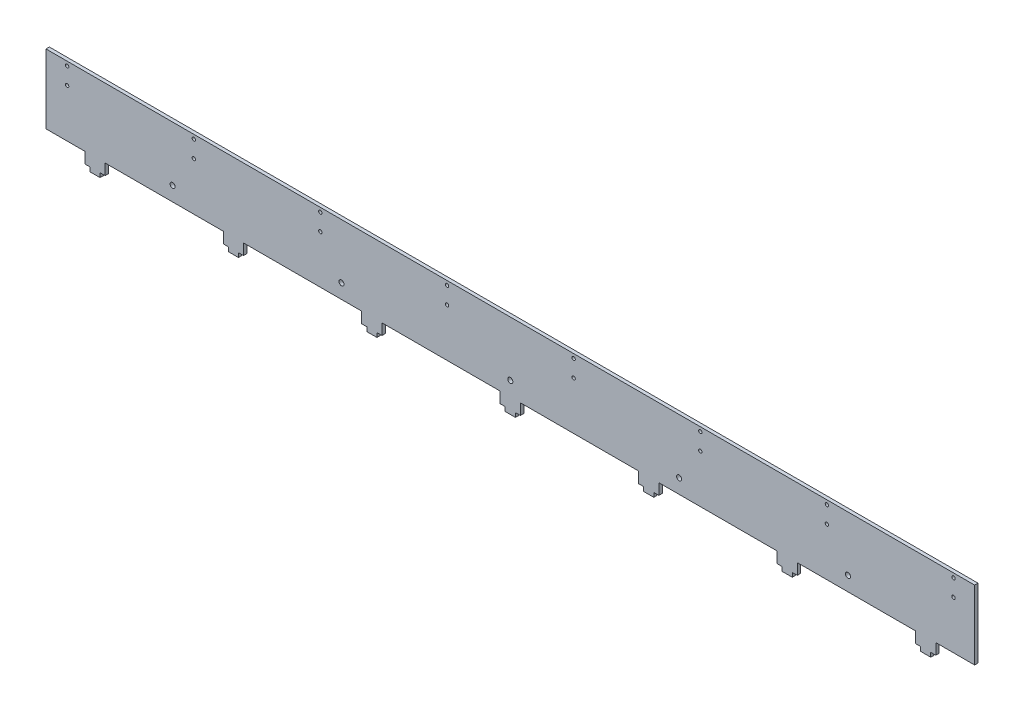
SolidWorks part; units mm, degrees
ref_plane "Спереди" through (0, 0, 0) normal (0, 0, 1) x (1, 0, 0)
ref_plane "Сверху" through (0, 0, 0) normal (0, 1, 0) x (1, 0, 0)
ref_plane "Справа" through (0, 0, 0) normal (1, 0, 0) x (0, 0, -1)
sketch "Эскиз1" plane through (0, 0, 0) normal (0, 0, 1) x (1, 0, 0)
  line L1 (-550, -47.5) -> (550, -47.5)
  line L2 (-550, -47.5) -> (-550, 47.5)
  line L3 (-550, 47.5) -> (550, 47.5)
  line L4 (550, -47.5) -> (550, 47.5)
  line L5 (0, 47.5) -> (0, -47.5) construction
  line L6 (-550, 0) -> (550, 0) construction
  point P0 (0, 0)
  dimension "D1" = 95
  dimension "D2" = 1100
extrude "Бобышка-Вытянуть1" add sketch "Эскиз1" along normal mid plane 4
sketch "Эскиз2" plane through (0, 0, 2) normal (0, 0, 1) x (1, 0, 0)
  line L0 (-550, -47.5) -> (550, -47.5) construction
  line L1 (-550, -47.5) -> (-504, -47.5)
  line L2 (-550, -47.5) -> (-550, -34.5)
  line L3 (-550, -34.5) -> (-504, -34.5)
  line L4 (-504, -47.5) -> (-504, -34.5)
  line L5 (550, -47.5) -> (504, -47.5)
  line L6 (550, -47.5) -> (550, -34.5)
  line L7 (550, -34.5) -> (504, -34.5)
  line L8 (504, -47.5) -> (504, -34.5)
  line L9 (-480, -34.5) -> (-340, -34.5)
  line L10 (-480, -34.5) -> (-480, -47.5)
  line L11 (-480, -47.5) -> (-340, -47.5)
  line L12 (-340, -34.5) -> (-340, -47.5)
  line L14 (-316, -34.5) -> (-176, -34.5)
  line L15 (-316, -34.5) -> (-316, -47.5)
  line L16 (-316, -47.5) -> (-176, -47.5)
  line L17 (-176, -34.5) -> (-176, -47.5)
  line L18 (-152, -34.5) -> (-12, -34.5)
  line L19 (-152, -34.5) -> (-152, -47.5)
  line L20 (-152, -47.5) -> (-12, -47.5)
  line L21 (-12, -34.5) -> (-12, -47.5)
  line L22 (12, -34.5) -> (152, -34.5)
  line L23 (12, -34.5) -> (12, -47.5)
  line L24 (12, -47.5) -> (152, -47.5)
  line L25 (152, -34.5) -> (152, -47.5)
  line L26 (176, -34.5) -> (316, -34.5)
  line L27 (176, -34.5) -> (176, -47.5)
  line L28 (176, -47.5) -> (316, -47.5)
  line L29 (316, -34.5) -> (316, -47.5)
  line L30 (340, -34.5) -> (480, -34.5)
  line L31 (340, -34.5) -> (340, -47.5)
  line L32 (340, -47.5) -> (480, -47.5)
  line L33 (480, -34.5) -> (480, -47.5)
  point P20 (-316, -41)
  point P25 (-152, -41)
  point P26 (152, -41)
  point P39 (340, -41)
  dimension "D1" = 13
  dimension "D5" = 24
  dimension "D6" = 140
  dimension "D7" = 24
  dimension "D2" = 24
  dimension "D3" = 140
  dimension "D4" = 140
  dimension "D8" = 24
  dimension "D9" = 140
  dimension "D10" = 24
  dimension "D11" = 140
  dimension "D12" = 24
  dimension "D13" = 140
  dimension "D14" = 24
extrude "Вырез-Вытянуть1" cut sketch "Эскиз2" against normal through all
sketch "Эскиз3" plane through (0, 0, 2) normal (0, 0, 1) x (1, 0, 0)
  line L0 (550, 47.5) -> (-550, 47.5) construction
  line L1 (-550, 47.5) -> (-550, -34.5) construction
  circle A0 centre (-525, 42.5) radius 2
  circle A1 centre (-525, 22.5) radius 2
  dimension "D1" = 4
  dimension "D2" = 5
  dimension "D3" = 20
  dimension "D4" = 25
extrude "Вырез-Вытянуть2" cut sketch "Эскиз3" against normal through all
pattern_linear "Линейный массив1" count 8 spacing 150 along (1, 0, 0) of "Вырез-Вытянуть2"
sketch "Эскиз4" plane through (0, 0, -2) normal (0, 0, -1) x (-1, 0, 0)
  circle A1 centre (-400, -17.5) radius 3
  circle A2 centre (-400, -17.5) radius 3
  dimension "D1" = 0
extrude "Вырез-Вытянуть3" cut sketch "Эскиз4" against normal through all
pattern_linear "Линейный массив2" count 5 spacing 200 along (-1, 0, 0) of "Вырез-Вытянуть3"
sketch "Эскиз5" plane through (0, -47.5, 0) normal (0, -1, 0) x (1, 0, 0)
  line L0 (492, -2) -> (492, 2) construction
  line L1 (480, 2) -> (504, 2) construction
  line L2 (328, -2) -> (328, 2) construction
  line L3 (316, -2) -> (340, -2) construction
  line L4 (504, 2) -> (480, 2)
  line L5 (480, 2) -> (480, -2)
  line L6 (480, -2) -> (504, -2)
  line L7 (504, -2) -> (504, 2)
  line L8 (498, 2) -> (486, 2)
  line L9 (486, 2) -> (486, -2)
  line L10 (486, -2) -> (498, -2)
  line L11 (498, -2) -> (498, 2)
  line L12 (316, 2) -> (340, 2) construction
  line L13 (164, -2) -> (164, 2) construction
  line L14 (316, -2) -> (340, -2)
  line L15 (340, -2) -> (340, 2)
  line L16 (340, 2) -> (316, 2)
  line L17 (316, 2) -> (316, -2)
  line L18 (322, -2) -> (334, -2)
  line L19 (334, -2) -> (334, 2)
  line L20 (334, 2) -> (322, 2)
  line L21 (322, 2) -> (322, -2)
  line L22 (152, -2) -> (176, -2) construction
  line L23 (152, 2) -> (176, 2) construction
  line L24 (0, -2) -> (0, 2) construction
  line L25 (176, 2) -> (152, 2)
  line L26 (152, 2) -> (152, -2)
  line L27 (152, -2) -> (176, -2)
  line L28 (176, -2) -> (176, 2)
  line L29 (170, 2) -> (158, 2)
  line L30 (158, 2) -> (158, -2)
  line L31 (158, -2) -> (170, -2)
  line L32 (170, -2) -> (170, 2)
  line L33 (-12, -2) -> (12, -2) construction
  line L34 (-12, 2) -> (12, 2) construction
  line L36 (-12, -2) -> (12, -2)
  line L37 (12, -2) -> (12, 2)
  line L38 (12, 2) -> (-12, 2)
  line L39 (-12, 2) -> (-12, -2)
  line L40 (-6, -2) -> (6, -2)
  line L41 (6, -2) -> (6, 2)
  line L42 (6, 2) -> (-6, 2)
  line L43 (-6, 2) -> (-6, -2)
  line L44 (-480, 2) -> (-504, 2) construction
  line L46 (-504, -2) -> (-480, -2) construction
  line L48 (-316, 2) -> (-340, 2) construction
  line L50 (-340, -2) -> (-316, -2) construction
  line L52 (-152, 2) -> (-176, 2) construction
  line L54 (-176, -2) -> (-152, -2) construction
  line L56 (-486, 2) -> (-498, 2)
  line L57 (-498, 2) -> (-498, -2)
  line L58 (-498, -2) -> (-486, -2)
  line L59 (-486, -2) -> (-486, 2)
  line L60 (-322, 2) -> (-334, 2)
  line L61 (-334, 2) -> (-334, -2)
  line L62 (-334, -2) -> (-322, -2)
  line L63 (-322, -2) -> (-322, 2)
  line L64 (-158, 2) -> (-170, 2)
  line L65 (-170, 2) -> (-170, -2)
  line L66 (-170, -2) -> (-158, -2)
  line L67 (-158, -2) -> (-158, 2)
  line L68 (-492, -2) -> (-492, 2) construction
  line L69 (-504, 2) -> (-480, 2) construction
  line L70 (-328, -2) -> (-328, 2) construction
  line L71 (-340, 2) -> (-316, 2) construction
  line L72 (-164, -2) -> (-164, 2) construction
  line L73 (-176, 2) -> (-152, 2) construction
  point P10 (0, 0)
  point P27 (0, 0)
  point P84 (0, 0)
  point P85 (-334, 0)
  point P94 (0, 0)
  point P95 (-159.9739, 2)
  point P96 (0, 0)
  dimension "D2" = 12
  dimension "D4" = 12
  dimension "D6" = 12
  dimension "D8" = 12
  dimension "D9" = 12
  dimension "D10" = 12
  dimension "D11" = 12
  dimension "D1" = 0
  dimension "D3" = 0
  dimension "D5" = 0
  dimension "D7" = 0
extrude "Бобышка-Вытянуть2" add sketch "Эскиз5" along normal blind 5
equation "\"D7@Эскиз2\"=\"D5@Эскиз2\""
equation "\"D2@Эскиз2\"=\"D5@Эскиз2\""
equation "\"D3@Эскиз2\"=\"D6@Эскиз2\""
equation "\"D4@Эскиз2\"=\"D6@Эскиз2\""
equation "\"D8@Эскиз2\"=\"D5@Эскиз2\""
equation "\"D9@Эскиз2\"=\"D6@Эскиз2\""
equation "\"D10@Эскиз2\"=\"D5@Эскиз2\""
equation "\"D11@Эскиз2\"=\"D6@Эскиз2\""
equation "\"D12@Эскиз2\"=\"D5@Эскиз2\""
equation "\"D13@Эскиз2\"=\"D6@Эскиз2\""
equation "\"D14@Эскиз2\"=\"D5@Эскиз2\""
